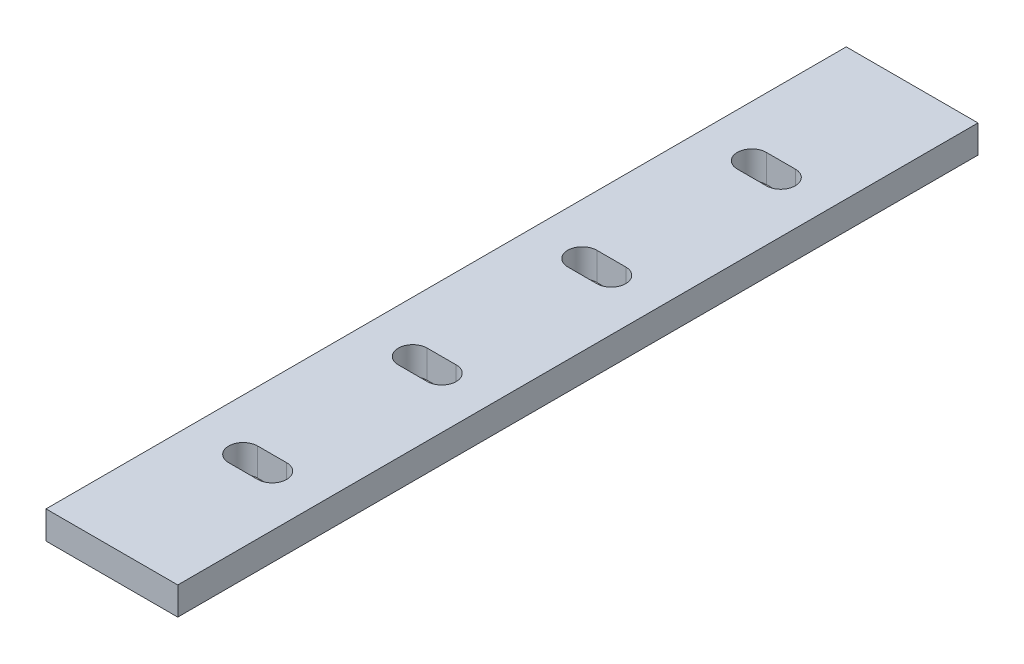
SolidWorks part; units mm, degrees
ref_plane "Front Plane" through (0, 0, 0) normal (0, 0, 1) x (1, 0, 0)
ref_plane "Top Plane" through (0, 0, 0) normal (0, 1, 0) x (1, 0, 0)
ref_plane "Right Plane" through (0, 0, 0) normal (1, 0, 0) x (0, 0, -1)
sketch "Sketch2" plane through (0, 0, 0) normal (0, 1, 0) x (1, 0, 0)
  line L0 (9.15, 16.6) -> (5.85, 16.6) construction
  line L1 (0, 0) -> (15, 0)
  line L2 (0, 0) -> (0, 91.1)
  line L3 (0, 91.1) -> (15, 91.1)
  line L4 (15, 0) -> (15, 91.1)
  line L5 (7.5, 0) -> (7.5, 91.1) construction
  line L6 (9.15, 14.95) -> (5.85, 14.95)
  line L7 (9.15, 18.25) -> (5.85, 18.25)
  line L8 (9.15, 35.9) -> (5.85, 35.9) construction
  line L9 (9.15, 34.25) -> (5.85, 34.25)
  line L10 (9.15, 37.55) -> (5.85, 37.55)
  line L11 (9.15, 55.2) -> (5.85, 55.2) construction
  line L12 (9.15, 53.55) -> (5.85, 53.55)
  line L13 (9.15, 56.85) -> (5.85, 56.85)
  line L14 (9.15, 74.5) -> (5.85, 74.5) construction
  line L15 (9.15, 72.85) -> (5.85, 72.85)
  line L16 (9.15, 76.15) -> (5.85, 76.15)
  arc A0 (9.15, 14.95) -> (9.15, 18.25) centre (9.15, 16.6) ccw
  arc A1 (5.85, 18.25) -> (5.85, 14.95) centre (5.85, 16.6) ccw
  arc A2 (9.15, 34.25) -> (9.15, 37.55) centre (9.15, 35.9) ccw
  arc A3 (5.85, 37.55) -> (5.85, 34.25) centre (5.85, 35.9) ccw
  arc A4 (9.15, 53.55) -> (9.15, 56.85) centre (9.15, 55.2) ccw
  arc A5 (5.85, 56.85) -> (5.85, 53.55) centre (5.85, 55.2) ccw
  arc A6 (9.15, 72.85) -> (9.15, 76.15) centre (9.15, 74.5) ccw
  arc A7 (5.85, 76.15) -> (5.85, 72.85) centre (5.85, 74.5) ccw
  point P9 (7.5, 16.6)
  point P14 (0, 0)
  point P17 (7.5, 35.9)
  point P22 (0, 0)
  point P23 (0, 0)
  point P24 (0, 0)
  point P27 (7.5, 55.2)
  point P32 (0, 0)
  point P33 (0, 0)
  point P36 (7.5, 74.5)
  point P41 (0, 0)
  point P42 (0, 0)
  point P43 (0, 0)
  dimension "D2" = 1.65
  dimension "D1" = 15
  dimension "D3" = 14.95
  dimension "D4" = 19.3
  dimension "D5" = 19.3
  dimension "D6" = 19.3
  dimension "D7" = 3.3
  dimension "D8" = 14.95
extrude "Boss-Extrude1" add sketch "Sketch2" along normal blind 3.175
